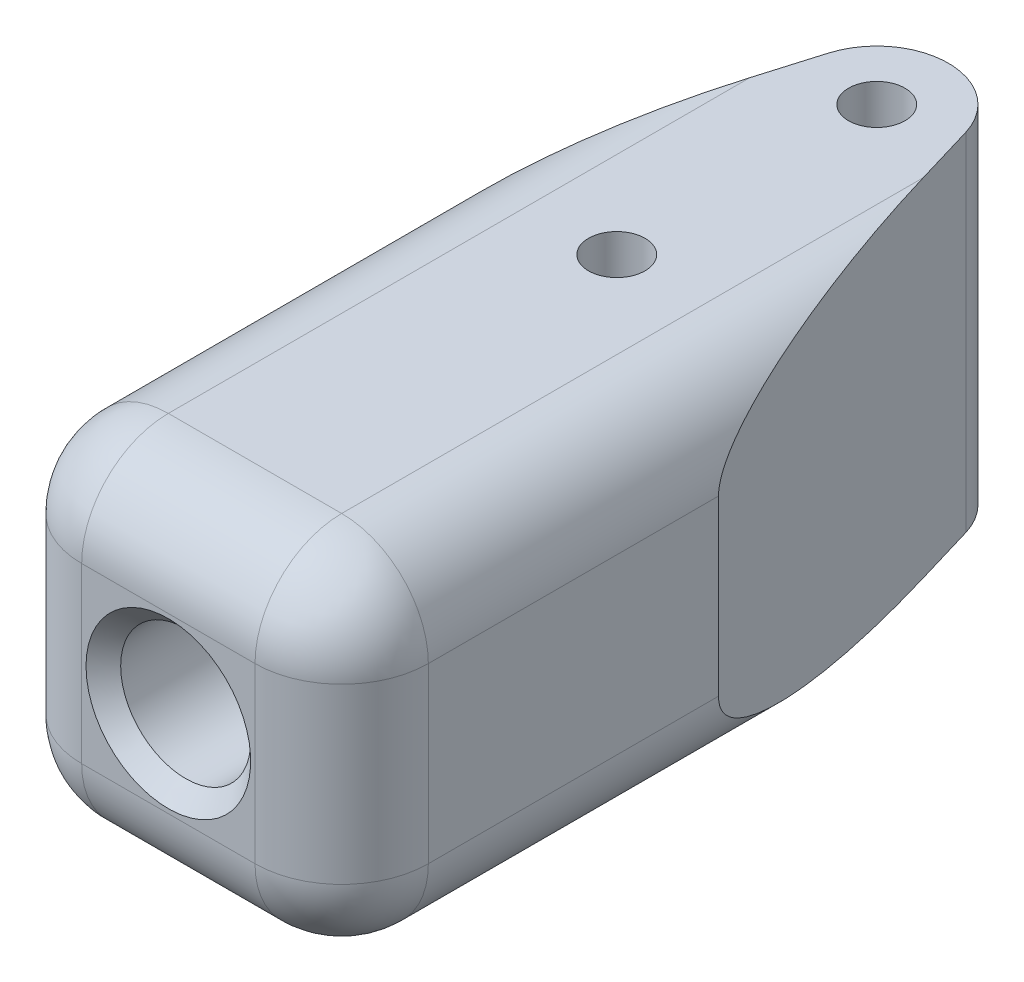
SolidWorks part; units mm, degrees
material "ABS"
ref_plane "Front Plane" through (0, 0, 0) normal (0, 0, 1) x (1, 0, 0)
ref_plane "Top Plane" through (0, 0, 0) normal (0, 1, 0) x (1, 0, 0)
ref_plane "Right Plane" through (0, 0, 0) normal (1, 0, 0) x (0, 0, -1)
sketch "Sketch1" plane through (0, 0, 0) normal (0, 0, 1) x (1, 0, 0)
  line L1 (12.7, 12.7) -> (-12.7, 12.7)
  line L2 (12.7, 12.7) -> (12.7, -12.7)
  line L3 (12.7, -12.7) -> (-12.7, -12.7)
  line L4 (-12.7, 12.7) -> (-12.7, -12.7)
  line L5 (12.7, 12.7) -> (-12.7, -12.7) construction
  line L6 (12.7, -12.7) -> (-12.7, 12.7) construction
  circle A0 centre (0, 0) radius 4.7625 construction
  dimension "D1" = 9.525
  dimension "D2" = 25.4
  dimension "D3" = 25.4
extrude "Boss-Extrude1" add sketch "Sketch1" along normal blind 57.15
sketch "Sketch2" plane through (0, 12.7, 0) normal (0, 1, 0) x (1, 0, 0)
  line L0 (0, 0) -> (0, -57.15) construction
  line L1 (12.7, -57.15) -> (-12.7, -57.15) construction
  line L2 (12.7, 0) -> (-12.7, 0) construction
  line L3 (-12.7, -29.5402) -> (12.7, -29.5402)
  line L4 (4.7625, -82.55) -> (-4.7625, -82.55) construction
  line L5 (4.7625, -82.55) -> (4.7625, -31.75) construction
  line L6 (4.7625, -31.75) -> (-4.7625, -31.75) construction
  line L7 (-4.7625, -82.55) -> (-4.7625, -31.75) construction
  line L8 (4.7625, -82.55) -> (-4.7625, -31.75) construction
  line L9 (4.7625, -31.75) -> (-4.7625, -82.55) construction
  line L10 (-12.7, -57.15) -> (-12.7, 0) construction
  line L11 (12.7, -57.15) -> (12.7, 0) construction
  line L12 (-12.7, -29.5402) -> (-5.0273, -3.7495)
  line L13 (12.7, -29.5402) -> (5.0273, -3.7495)
  line L14 (-12.7, -29.5402) -> (-12.7, 0)
  line L15 (12.7, 0) -> (-12.7, 0)
  line L16 (12.7, -29.5402) -> (12.7, 0)
  circle A0 centre (0, -5.2451) radius 2.0701
  circle A1 centre (0, -24.2951) radius 2.0701
  arc A2 (5.0273, -3.7495) -> (-5.0273, -3.7495) centre (0, -5.2451) ccw
  circle A3 centre (0, -24.2951) radius 5.2451 construction
  line M3 (12.7, 0) -> (-12.7, 0)
  line M4 (-12.7, 0) -> (-12.7, -57.15)
  line M6 (12.7, -57.15) -> (12.7, 0)
  dimension "D1" = 4.1402
  dimension "D2" = 3.175
  dimension "D3" = 19.05
  dimension "D4" = 9.525
  dimension "D5" = 50.8
extrude "Cut-Extrude1" cut sketch "Sketch2" against normal through all and the other way through all contours A2 L13 M6 M3 | A1 | A0 | A2 L15 L12 M4 region at (-9.63, 12.7, 9.6499) region at (9.63, 12.7, 9.6499) region at (0, 12.7, 5.2451) region at (0, 12.7, 24.2951)
sketch "Sketch4" plane through (0, 0, 57.15) normal (0, 0, 1) x (1, 0, 0)
  circle A0 centre (0, 0) radius 4.7625
  dimension "D1" = 9.525
extrude "Cut-Extrude2" cut sketch "Sketch4" against normal blind 25.4
chamfer "Chamfer1" distance 1.27 angle 45 1 edges at (4.7625, 0, 57.15)
fillet "Fillet1" radius 6.35 5 edges at (-12.7, -12.7, 43.3451) (12.7, -12.7, 43.3451) (0, -12.7, 57.15) (-12.7, 0, 57.15) (12.7, 0, 57.15)
fillet "Fillet2" radius 6.35 5 edges at (12.7, 12.7, 40.1701) (10.8401, 12.7, 55.2901) (0, 12.7, 57.15) (-10.8401, 12.7, 55.2901) (-12.7, 12.7, 40.1701)
